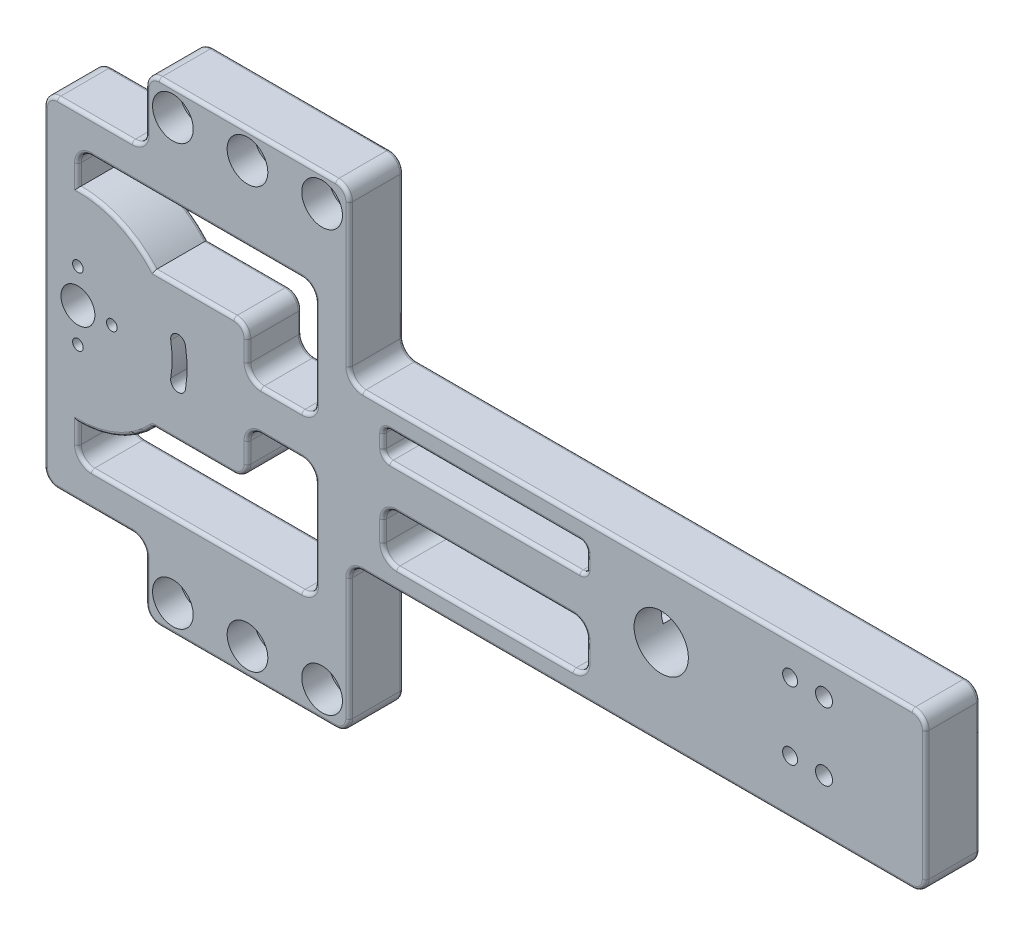
SolidWorks part; units mm, degrees
material "6061 Alloy"
ref_plane "Front Plane" through (0, 0, 0) normal (0, 0, 1) x (1, 0, 0)
ref_plane "Top Plane" through (0, 0, 0) normal (0, 1, 0) x (1, 0, 0)
ref_plane "Right Plane" through (0, 0, 0) normal (1, 0, 0) x (0, 0, -1)
sketch "Sketch1" plane through (0, 0, 0) normal (0, 0, 1) x (1, 0, 0)
  line L0 (-65, 0) -> (65, 0) construction
  line L5 (0, 35) -> (0, -35) construction
  line L6 (-65, 25) -> (-65, -25)
  line L7 (-65, -25) -> (-50, -25)
  line L8 (-50, -25) -> (-50, -35)
  line L9 (-50, -35) -> (-20, -35)
  line L10 (-20, -35) -> (-20, -13)
  line L11 (-20, -13) -> (65, -13)
  line L12 (65, -13) -> (65, 10)
  line L13 (65, 10) -> (-20, 10)
  line L14 (-20, 10) -> (-20, 35)
  line L15 (-20, 35) -> (-50, 35)
  line L16 (-50, 35) -> (-50, 25)
  line L17 (-50, 25) -> (-65, 25)
  dimension "D1" = 70
  dimension "D2" = 130
  dimension "D3" = 15
  dimension "D4" = 10
  dimension "D5" = 10
  dimension "D6" = 13
  dimension "D7" = 30
extrude "Boss-Extrude1" add sketch "Sketch1" along normal blind 8 contours L17 L6 L7 L8 L9 L10 L11 L12 L13 L14 L15 L16
sketch "Sketch3" plane through (0, 0, 8) normal (0, 0, 1) x (1, 0, 0)
  line L0 (-50, -25) -> (-50, -35) construction
  line L1 (-50, -35) -> (-20, -35) construction
  circle A0 centre (-46, -31) radius 3
  circle A1 centre (-35, -31) radius 3
  circle A2 centre (-24, -31) radius 3
  circle A3 centre (-46, -31) radius 1.6
  circle A4 centre (-35, -31) radius 1.6
  circle A5 centre (-24, -31) radius 1.6
  dimension "D1" = 6
  dimension "D2" = 3.2
  dimension "D5" = 11
  dimension "D3" = 15
  dimension "D4" = 11
  dimension "D6" = 4
extrude "Cut-Extrude1" cut sketch "Sketch3" against normal blind 4 contours A0 | A1 | A2
extrude "Cut-Extrude2" cut sketch "Sketch3<3>" against normal blind 8 contours A3 | A4 | A5
sketch "Sketch3<3>" plane through (0, 0, 8) normal (0, 0, 1) x (1, 0, 0) same geometry as "Sketch3"
mirror "Mirror1" about plane through (0, 0, 0) normal (0, 1, 0) of "Cut-Extrude1", "Cut-Extrude2"
sketch "Sketch4" plane through (0, 0, 0) normal (0, 0, -1) x (-1, 0, 0)
  line L0 (65, 25) -> (65, -25) construction
  line L1 (65, 6.245) -> (65, -6.245)
  arc A0 (65, 6.245) -> (65, -6.245) centre (60, 0) ccw
  circle A1 centre (60, 0) radius 2.5
  circle A2 centre (60, 5) radius 0.7835
  circle A3 centre (55, 0) radius 0.7835
  circle A4 centre (60, -5) radius 0.7835
  dimension "D1" = 16
  dimension "D3" = 5
  dimension "D4" = 1.567
  dimension "D5" = 5
  dimension "D6" = 5
  dimension "D7" = 5
  dimension "D2" = 5
extrude "Cut-Extrude3" cut sketch "Sketch4" against normal blind 4
extrude "Cut-Extrude4" cut sketch "Sketch4<2>" against normal blind 8 contours A2 | A3 | A1 | A4
sketch "Sketch4<2>" plane through (0, 0, 0) normal (0, 0, -1) x (-1, 0, 0) same geometry as "Sketch4"
fillet "Fillet1" radius 2 12 edges at (-65, -25, 4) (-50, -25, 4) (-50, -35, 4) (-20, -35, 4) (-20, -13, 4) (65, -13, 4) (65, 10, 4) (-20, 10, 4) (-20, 35, 4) (-50, 35, 4) (-50, 25, 4) (-65, 25, 4)
sketch "Sketch6" plane through (0, 0, 0) normal (0, 0, -1) x (-1, 0, 0)
  line L0 (-65, -11) -> (-65, 8) construction
  line L1 (-63, 10) -> (18, 10) construction
  circle A0 centre (-45, 5) radius 1.1
  circle A1 centre (-45, 5) radius 2
  circle A2 centre (-45, -5) radius 1.1
  circle A3 centre (-45, -5) radius 2
  dimension "D1" = 4
  dimension "D2" = 2.2
  dimension "D3" = 20
  dimension "D4" = 5
  dimension "D5" = 10
extrude "Cut-Extrude6" cut sketch "Sketch6" against normal blind 4 contours A1 | A3
extrude "Cut-Extrude7" cut sketch "Sketch6<3>" against normal blind 8 contours A0 | A2
sketch "Sketch6<3>" plane through (0, 0, 0) normal (0, 0, -1) x (-1, 0, 0) same geometry as "Sketch6"
sketch "Sketch7" plane through (0, 0, 0) normal (0, 0, -1) x (-1, 0, 0)
  line L0 (-65, -11) -> (-65, 8) construction
  line L1 (-31, 0) -> (-21, 0) construction
  line L2 (-31, 1.5) -> (-21, 1.5)
  line L3 (-31, -1.5) -> (-21, -1.5)
  circle A0 centre (-26, 0) radius 4
  arc A1 (-31, 1.5) -> (-31, -1.5) centre (-31, 0) ccw
  arc A2 (-21, -1.5) -> (-21, 1.5) centre (-21, 0) ccw
  point P7 (-26, 0)
  dimension "D2" = 8
  dimension "D3" = 1.5
  dimension "D1" = 39
  dimension "D4" = 5
extrude "Cut-Extrude8" cut sketch "Sketch7" against normal blind 8 contours A0
extrude "Cut-Extrude9" cut sketch "Sketch7<3>" against normal blind 4 contours L2 A2 L3 A1
sketch "Sketch7<3>" plane through (0, 0, 0) normal (0, 0, -1) x (-1, 0, 0) same geometry as "Sketch7"
sketch "Sketch9" plane through (0, 0, 0) normal (0, 0, -1) x (-1, 0, 0)
  line L0 (-15, 0) -> (65, 0) construction
  line L1 (65, -6.245) -> (65, 6.245) construction
  line L2 (35, 10) -> (35, 3)
  line L3 (65, 23) -> (65, 6.245) construction
  line L5 (-63, 10) -> (18, 10) construction
  line L6 (35, 10) -> (48.8197, 10)
  line L7 (35, -10) -> (48.8197, -10)
  line L8 (60, 15) -> (60, 20)
  line L9 (60, 20) -> (25, 20)
  line L10 (25, 20) -> (25, 3)
  line L11 (52, 25) -> (63, 25) construction
  line L12 (20, 12) -> (20, 33) construction
  line L13 (25, 3) -> (35, 3)
  line L14 (25, -3) -> (35, -3)
  line L15 (60, -15) -> (60, -20)
  line L16 (60, -20) -> (25, -20)
  line L17 (35, -3) -> (35, -10)
  line L18 (25, -3) -> (25, -20)
  line L19 (-15, 7) -> (15, 7)
  line L20 (-15, 7) -> (-15, 3)
  line L21 (-15, 3) -> (15, 3)
  line L22 (15, 7) -> (15, 3)
  line L23 (-15, -10) -> (15, -10)
  line L24 (-15, -10) -> (-15, -3)
  line L25 (-15, -3) -> (15, -3)
  line L26 (15, -10) -> (15, -3)
  line L27 (18, -13) -> (-63, -13) construction
  arc A0 (60, 15) -> (48.8197, 10) centre (60, 0) ccw
  arc A1 (48.8197, -10) -> (60, -15) centre (60, 0) ccw
  point P30 (20, 0)
  dimension "D3" = 30
  dimension "D1" = 30
  dimension "D2" = 20
  dimension "D4" = 15
  dimension "D5" = 5
  dimension "D6" = 5
  dimension "D7" = 3
  dimension "D8" = 10
  dimension "D9" = 10
  dimension "D10" = 10
  dimension "D11" = 0
  dimension "D12" = 0
  dimension "D13" = 3
  dimension "D14" = 3
  dimension "D15" = 3
  dimension "D16" = 3
extrude "Cut-Extrude10" cut sketch "Sketch9" against normal blind 8
fillet "Fillet2" radius 2 14 edges at (-25, -20, 4) (-35, -10, 4) (-35, -3, 4) (-25, -3, 4) (-35, 10, 4) (-35, 3, 4) (-25, 3, 4) (-60, 20, 4) (-25, 20, 4) (-15, -10, 4) (15, -10, 4) (-15, -3, 4) (15, -3, 4) (-60, -20, 4)
fillet "Fillet3" radius 1 4 edges at (-15, 3, 4) (-15, 7, 4) (15, 7, 4) (15, 3, 4)
fillet "Fillet4" radius 0.5 133 edges at (-42.5, -20, 8) (-25.5858, -19.4142, 8) (-25, -11.5, 8) (-25.5858, -3.5858, 8) (-30, -3, 8) (-34.4142, -3.5858, 8) (-35, -6.5, 8) (-35.5858, -9.4142, 8) (-14.7071, 3.2929, 8) (0, 3, 8) (14.7071, 3.2929, 8) (15, 5, 8) (14.7071, 6.7071, 8) (0, 7, 8) (-14.7071, 6.7071, 8) (-14.4142, -3.5858, 8) (-15, -6.5, 8) (-14.4142, -9.4142, 8) (0, -10, 8) (14.4142, -9.4142, 8) (15, -6.5, 8) (14.4142, -3.5858, 8) (-60, 16.5, 8) (-59.4142, 19.4142, 8) (-42.5, 20, 8) (-25.5858, 19.4142, 8) (-25, 11.5, 8) (-25.5858, 3.5858, 8) (-30, 3, 8) (-34.4142, 3.5858, 8) (-35, 6.5, 8) (-35.5858, 9.4142, 8) (-20.5858, 34.4142, 8) (-20, 22.5, 8) (-19.4142, 10.5858, 8) (22.5, 10, 8) (64.4142, 9.4142, 8) (65, -1.5, 8) (64.4142, -12.4142, 8) (22.5, -13, 8) (-19.4142, -13.5858, 8) (-20, -24, 8) (-20.5858, -34.4142, 8) (-35, -35, 8) (-49.4142, -34.4142, 8) (-50, -30, 8) (-50.5858, -25.5858, 8) (-57.5, -25, 8) (-64.4142, -24.4142, 8) (-65, 0, 8) (-64.4142, 24.4142, 8) (-57.5, 25, 8) (-50.5858, 25.5858, 8) (-50, 30, 8) (-49.4142, 34.4142, 8) (-35.5858, -9.4142, 0) (-35, -6.5, 0) (-34.4142, -3.5858, 0) (-42.5, -20, 0) (-25.5858, -19.4142, 0) (-25, -11.5, 0) (-25.5858, -3.5858, 0) (-60, 16.5, 0) (-59.4142, 19.4142, 0) (-42.5, 20, 0) (-25.5858, 19.4142, 0) (-42.9098, 10, 0) (-35.5858, 9.4142, 0) (-35, 6.5, 0) (-34.4142, 3.5858, 0) (-30, 3, 0) (-25.5858, 3.5858, 0) (-14.4142, -3.5858, 0) (-15, -6.5, 0) (-14.4142, -9.4142, 0) (0, -10, 0) (14.4142, -9.4142, 0) (15, -6.5, 0) (14.4142, -3.5858, 0) (14.7071, 3.2929, 0) (15, 5, 0) (14.7071, 6.7071, 0) (0, 7, 0) (-14.7071, 6.7071, 0) (-15, 5, 0) (-14.7071, 3.2929, 0) (-65, -14.6225, 0) (-64.4142, -24.4142, 0) (-57.5, -25, 0) (-50.5858, -25.5858, 0) (-50, -30, 0) (-49.4142, -34.4142, 0) (-35, -35, 0) (-20.5858, -34.4142, 0) (-20, -24, 0) (-19.4142, -13.5858, 0) (22.5, -13, 0) (64.4142, -12.4142, 0) (-65, 14.6225, 0) (-64.4142, 24.4142, 0) (-57.5, 25, 0) (-50.5858, 25.5858, 0) (-50, 30, 0) (-49.4142, 34.4142, 0) (-35, 35, 0) (-20.5858, 34.4142, 0) (-20, 22.5, 0) (-19.4142, 10.5858, 0) (22.5, 10, 0) (64.4142, 9.4142, 0) (-48.8197, -10, 4) (-42.9098, -10, 8) (-42.9098, -10, 0) (-15, 5, 8) (0, -3, 8) (-60, -16.5, 8) (-53.8763, -13.6931, 8) (-53.8763, 13.6931, 8) (-42.9098, 10, 8) (-35, 35, 8) (-52, 0, 0) (-65, -6.245, 2) (-65, 6.245, 2) (-53.8763, 13.6931, 0) (-53.8763, -13.6931, 0) (-30, -3, 0) (-25, 11.5, 0) (0, -3, 0) (0, 3, 0) (65, -1.5, 0) (-59.4142, -19.4142, 8) (-60, -16.5, 0) (-59.4142, -19.4142, 0)
hole_wizard "Ø3.0mm Dowel Hole1" positions "Sketch10" profile "Sketch11" hole size "Ø3.0" standard "ANSI Metric"
sketch "Sketch10" plane through (0, -13, 0) normal (0, -1, 0) x (-1, 0, 0)
  line L0 (18, -8) -> (-63, -8) construction
  line L1 (-65, -7.5) -> (-65, -0.5) construction
  point P3 (-38, -4)
  point P9 (-53, -4)
  dimension "D1" = 4
  dimension "D2" = 12
  dimension "D3" = 15
sketch "Sketch11" plane through (38, -13, 4) normal (1, 0, 0) x (0, 0, -1)
  line L0 (0, 0) -> (0, 7)
  line L1 (0, 7) -> (1.5, 6.0987)
  line L2 (1.5, 6.0987) -> (1.5, 0)
  line L5 (1.5, 0) -> (0, 0)
  line L10 (0, 7) -> (-1.5, 6.0987) construction
  line L11 (0, -6.35) -> (0, 107.95) construction
  dimension "Hole Dia." = 3
  dimension "Hole Depth" = 7
  dimension "Drill Angle" = 118
thread "Thread1" pitch 0.5 method extrude trim with start face yes trim with end face yes profile "Thread Profile1" start angle 0, offset 1, length 10, pitch 0.5, diameter 3
ref_plane "Plane1" through (54.5, -14, 4) normal (0, 0, 1) x (1, 0, 0)
sketch "Thread Profile1" plane through (54.5, -14, 4) normal (0, 0, 1) x (1, 0, 0)
  line L0 (0, 0) -> (0, 0.5) construction
  line L11 (0, 0) -> (0, 0.4375)
  line L12 (0, 0.4375) -> (-0.2706, 0.2812)
  line L13 (-0.2706, 0.2812) -> (-0.2706, 0.1562)
  line L15 (-0.2706, 0.1562) -> (0, 0)
  line L17 (-0.2706, 0.2187) -> (0, 0.2187) construction
  point P2 (0, 0)
  dimension "Pitch" = 0.5
  dimension "Profile_Angle" = 60
  dimension "Profile_Land" = 0.125
  dimension "Profile_Height" = 0.2706
thread "Thread2" pitch 0.5 method extrude trim with start face yes trim with end face yes profile "Thread Profile2" start angle 0, offset 1, length 10, pitch 0.5, diameter 3
ref_plane "Plane2" through (39.5, -14, 4) normal (0, 0, 1) x (1, 0, 0)
sketch "Thread Profile2" plane through (39.5, -14, 4) normal (0, 0, 1) x (1, 0, 0)
  line L0 (0, 0) -> (0, 0.5) construction
  line L11 (0, 0) -> (0, 0.4375)
  line L12 (0, 0.4375) -> (-0.2706, 0.2812)
  line L13 (-0.2706, 0.2812) -> (-0.2706, 0.1562)
  line L15 (-0.2706, 0.1562) -> (0, 0)
  line L17 (-0.2706, 0.2187) -> (0, 0.2187) construction
  point P2 (0, 0)
  dimension "Pitch" = 0.5
  dimension "Profile_Angle" = 60
  dimension "Profile_Land" = 0.125
  dimension "Profile_Height" = 0.2706
hole_wizard "Ø2.5mm Dowel Hole1" positions "Sketch16" profile "Sketch17" hole size "Ø2.5" standard "ANSI Metric"
sketch "Sketch16" plane through (0, -13, 0) normal (0, -1, 0) x (-1, 0, 0)
  line L0 (18, -8) -> (-63, -8) construction
  point P0 (-48, -4)
  point P2 (-43, -4)
  dimension "D1" = 5
  dimension "D2" = 5
  dimension "D3" = 4
sketch "Sketch17" plane through (48, -13, 4) normal (1, 0, 0) x (0, 0, -1)
  line L0 (0, 0) -> (0, 4.7511)
  line L1 (0, 4.7511) -> (1.25, 4)
  line L2 (1.25, 4) -> (1.25, 0)
  line L5 (1.25, 0) -> (0, 0)
  line L10 (0, 4.7511) -> (-1.25, 4) construction
  line L11 (0, -6.35) -> (0, 107.95) construction
  dimension "Hole Dia." = 2.5
  dimension "Hole Depth" = 4
  dimension "Drill Angle" = 118
hole_wizard "Ø2.5mm Dowel Hole2" positions "Sketch19" profile "Sketch20" hole size "Ø2.5" standard "ANSI Metric"
sketch "Sketch19" plane through (0, 0, 0) normal (0, 0, -1) x (-1, 0, 0)
  line L0 (22, 35) -> (48, 35) construction
  line L1 (48, -35) -> (22, -35) construction
  circle A1 centre (35, 31) radius 1.6 construction
  circle A2 centre (35, -31) radius 1.6 construction
  point P0 (29.5, 31)
  point P2 (40.5, 31)
  point P4 (29.5, -31)
  point P6 (40.5, -31)
  dimension "D1" = 5.5
  dimension "D6" = 5.5
  dimension "D2" = 5.5
  dimension "D3" = 4
  dimension "D4" = 4
  dimension "D5" = 5.5
sketch "Sketch20" plane through (-29.5, 31, 0) normal (1, 0, 0) x (0, 1, 0)
  line L0 (0, 0) -> (0, 4.7511)
  line L1 (0, 4.7511) -> (1.25, 4)
  line L2 (1.25, 4) -> (1.25, 0)
  line L5 (1.25, 0) -> (0, 0)
  line L10 (0, 4.7511) -> (-1.25, 4) construction
  line L11 (0, -6.35) -> (0, 107.95) construction
  dimension "Hole Dia." = 2.5
  dimension "Hole Depth" = 4
  dimension "Drill Angle" = 118
sketch "Sketch21" plane through (0, 0, 0) normal (0, 0, -1) x (-1, 0, 0)
  line L0 (0, 0) -> (60, 0) construction
  arc A0 (45.2279, 2.6047) -> (45.2279, -2.6047) centre (60, 0) ccw construction
  arc A1 (43.2583, 2.952) -> (43.2583, -2.952) centre (60, 0) ccw
  arc A2 (47.1975, 2.2574) -> (47.1975, -2.2574) centre (60, 0) ccw
  arc A3 (47.1975, 2.2574) -> (43.2583, 2.952) centre (45.2279, 2.6047) ccw
  arc A4 (43.2583, -2.952) -> (47.1975, -2.2574) centre (45.2279, -2.6047) ccw
  arc A5 (45.2279, 2.6047) -> (45.2279, -2.6047) centre (60, 0) ccw construction
  arc A6 (44.1446, 2.7957) -> (44.1446, -2.7957) centre (60, 0) ccw
  arc A7 (46.3112, 2.4137) -> (46.3112, -2.4137) centre (60, 0) ccw
  arc A8 (46.3112, 2.4137) -> (44.1446, 2.7957) centre (45.2279, 2.6047) ccw
  arc A9 (44.1446, -2.7957) -> (46.3112, -2.4137) centre (45.2279, -2.6047) ccw
  point P4 (45, 0)
  point P9 (45, 0)
  dimension "D2" = 2
  dimension "D4" = 1.1
  dimension "D1" = 20
  dimension "D3" = 15
extrude "Cut-Extrude11" cut sketch "Sketch21" against normal blind 4 contours A3 A1 A4 A2
extrude "Cut-Extrude12" cut sketch "Sketch21<3>" against normal blind 8 contours A8 A6 A9 A7
sketch "Sketch21<3>" plane through (0, 0, 0) normal (0, 0, -1) x (-1, 0, 0) same geometry as "Sketch21"
hole_wizard "Ø2.5mm Dowel Hole3" positions "Sketch23" profile "Sketch24" hole size "Ø2.5" standard "ANSI Metric"
sketch "Sketch23" plane through (0, 0, 8) normal (0, 0, 1) x (1, 0, 0)
  line L0 (-18, 10) -> (63, 10) construction
  circle A0 centre (45, 5) radius 1.1 construction
  point P0 (50, 5)
  point P2 (50, -5)
  point P7 (0, 0)
  dimension "D1" = 5
  dimension "D2" = 10
  dimension "D3" = 5
sketch "Sketch24" plane through (50, 5, 8) normal (1, 0, 0) x (0, -1, 0)
  line L0 (0, 0) -> (0, 4.7511)
  line L1 (0, 4.7511) -> (1.25, 4)
  line L2 (1.25, 4) -> (1.25, 0)
  line L5 (1.25, 0) -> (0, 0)
  line L10 (0, 4.7511) -> (-1.25, 4) construction
  line L11 (0, -6.35) -> (0, 107.95) construction
  dimension "Hole Dia." = 2.5
  dimension "Hole Depth" = 4
  dimension "Drill Angle" = 118
